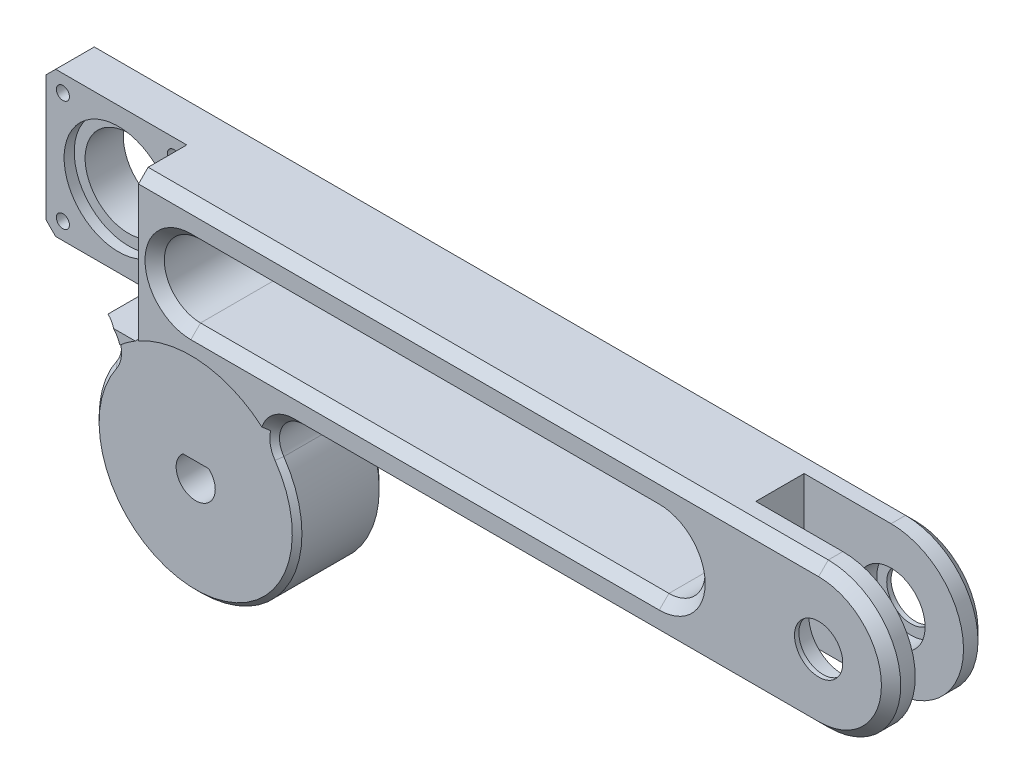
SolidWorks part; units mm, degrees
ref_plane "前视基准面" through (0, 0, 0) normal (0, 0, 1) x (1, 0, 0)
ref_plane "上视基准面" through (0, 0, 0) normal (0, 1, 0) x (1, 0, 0)
ref_plane "右视基准面" through (0, 0, 0) normal (1, 0, 0) x (0, 0, -1)
sketch "草图1" plane through (0, 0, 0) normal (0, 0, 1) x (1, 0, 0)
  line L0 (0, 15) -> (170, 15)
  line L1 (0, -15) -> (18.6465, -15)
  line L2 (0, -15) -> (0, 15)
  line L3 (61.3535, -15) -> (170, -15)
  line L4 (170, 0) -> (40, -34.8334) construction
  arc A1 (170, -15) -> (170, 15) centre (170, 0) ccw
  arc A2 (22.753, -22.8526) -> (57.247, -22.8526) centre (40, -34.8334) ccw
  arc A3 (18.6465, -15) -> (22.753, -22.8526) centre (18.6465, -20) cw
  arc A4 (61.3535, -15) -> (57.247, -22.8526) centre (61.3535, -20) ccw
  dimension "D1" = 15
  dimension "D3" = 42
  dimension "D6" = 5
  dimension "D7" = 5
  dimension "D2" = 170
  dimension "D4" = 75
  dimension "D5" = 40
extrude "凸台-拉伸1" add sketch "草图1" along normal blind 20
chamfer "倒角1" distance 2 angle 45 2 edges at (0, -15, 10) (0, 15, 10)
sketch "草图5" plane through (0, 0, 0) normal (0, 0, -1) x (-1, 0, 0)
  circle A0 centre (-170, 0) radius 5
  dimension "D1" = 10
extrude "切除-拉伸4" cut sketch "草图5" against normal blind 5
sketch "草图3" plane through (0, 15, 0) normal (0, 1, 0) x (1, 0, 0)
  line L0 (170, -20) -> (170, 0) construction
  line L1 (188, -5) -> (152, -5)
  line L2 (188, -5) -> (188, -15)
  line L3 (188, -15) -> (152, -15)
  line L4 (152, -5) -> (152, -15)
  line L5 (188, -5) -> (152, -15) construction
  line L6 (188, -15) -> (152, -5) construction
  point P0 (170, -10)
  dimension "D1" = 10
  dimension "D2" = 18
extrude "切除-拉伸2" cut sketch "草图3" against normal through all
sketch "草图4" plane through (0, 0, 0) normal (0, 0, -1) x (-1, 0, 0)
  line L0 (-40, 0) -> (-137, 0) construction
  line L1 (-40, -7.5) -> (-137, -7.5)
  line L2 (-40, 7.5) -> (-137, 7.5)
  line L3 (0, 13) -> (0, -13) construction
  arc A0 (-40, -7.5) -> (-40, 7.5) centre (-40, 0) ccw
  arc A1 (-137, 7.5) -> (-137, -7.5) centre (-137, 0) ccw
  point P3 (-88.5, 0)
  dimension "D1" = 15
  dimension "D2" = 40
  dimension "D3" = 15
extrude "切除-拉伸3" cut sketch "草图4" against normal through all
chamfer "倒角2" distance 2 angle 45 8 edges at (144.5, 0, 20) (88.5, 7.5, 20) (88.5, -7.5, 20) (32.5, 0, 20) (144.5, 0, 0) (88.5, 7.5, 0) (88.5, -7.5, 0) (32.5, 0, 0)
chamfer "倒角3" distance 2 angle 45 7 edges at (10.3233, -15, 0) (23.0773, -17.683, 0) (40, -55.8334, 0) (56.9227, -17.683, 0) (115.6767, -15, 0) (185, 0, 0) (86, 15, 0)
chamfer "倒角4" distance 2 angle 45 7 edges at (10.3233, -15, 20) (23.0773, -17.683, 20) (40, -55.8334, 20) (56.9227, -17.683, 20) (115.6767, -15, 20) (185, 0, 20) (86, 15, 20)
ref_plane "基准面1" through (0, 0, 10) normal (0, 0, -1) x (-1, 0, 0)
mirror "镜向1" about plane through (0, 0, 10) normal (0, 0, -1) of "切除-拉伸4"
sketch "草图6" plane through (0, 0, 10) normal (0, 0, -1) x (-1, 0, 0)
  point P0 (-40, -34.8334)
sketch "草图7" plane through (0, 0, 10) normal (0, 0, -1) x (-1, 0, 0)
  line L0 (-170, 0) -> (-40, -34.8334) construction
sketch "草图8" plane through (0, 0, 0) normal (0, 0, -1) x (-1, 0, 0)
  line L0 (-170, 0) -> (-15, 0) construction
  line L2 (-0.85, -15.5) -> (-29.15, -15.5)
  line L3 (-0.85, -15.5) -> (-0.85, 15.5)
  line L4 (-0.85, 15.5) -> (-29.15, 15.5)
  line L5 (-29.15, -15.5) -> (-29.15, 15.5)
  line L6 (-0.85, -15.5) -> (-29.15, 15.5) construction
  line L7 (-0.85, 15.5) -> (-29.15, -15.5) construction
  point P0 (-15, 0)
  dimension "D1" = 155
  dimension "D2" = 28.3
  dimension "D3" = 31
extrude "切除-拉伸5" cut sketch "草图8" along normal blind 10 from surface starting at face at (165, 0, 20)
sketch "草图9" plane through (0, 0, 10) normal (0, 0, 1) x (1, 0, 0)
  line L1 (3.5, -11.5) -> (26.5, -11.5)
  line L2 (3.5, -11.5) -> (3.5, 11.5)
  line L3 (3.5, 11.5) -> (26.5, 11.5)
  line L4 (26.5, -11.5) -> (26.5, 11.5)
  line L5 (3.5, -11.5) -> (26.5, 11.5) construction
  line L6 (3.5, 11.5) -> (26.5, -11.5) construction
  circle A0 centre (15, 0) radius 11.25
  circle A1 centre (26.5, 11.5) radius 1.35
  circle A2 centre (3.5, 11.5) radius 1.35
  circle A3 centre (3.5, -11.5) radius 1.35
  circle A4 centre (26.5, -11.5) radius 1.35
  line M5 (2, 15) -> (0.85, 13.85)
  line M7 (0.85, -13.85) -> (2, -15)
  dimension "D1" = 22.5
  dimension "D3" = 2.7
  dimension "D2" = 23
  dimension "D4" = 23
extrude "切除-拉伸6" cut sketch "草图9" against normal blind 2.1 contours A0 region at (15, 0, 10)
extrude "切除-拉伸7" cut sketch "草图9<3>" against normal through all contours L3 A2 L2 M5 | L4 A1 L3 | L3 A1 L4 | L1 A4 L4 | L2 A2 L3 | L4 A4 L1 | L2 A3 L1 M7 | L1 A3 L2 | A2 region at (4.073, -10.927, 10) region at (3.309, -11.691, 10) region at (25.927, -10.927, 10) region at (26.691, -11.691, 10) region at (3.309, 11.691, 10) region at (4.073, 10.927, 10) region at (25.927, 10.927, 10) region at (26.691, 11.691, 10)
sketch "草图9<3>" plane through (0, 0, 10) normal (0, 0, 1) x (1, 0, 0) same geometry as "草图9"
sketch "草图10" plane through (0, 0, 20) normal (0, 0, 1) x (1, 0, 0)
  line L0 (40, -34.8334) -> (40, -30.7834) construction
  line L1 (37.3354, -31.7834) -> (42.6646, -31.7834)
  circle A0 centre (40, -34.8334) radius 4.05
  dimension "D1" = 8.1
  dimension "D2" = 3.05
extrude "切除-拉伸8" cut sketch "草图10" against normal through all contours L1 A0 region at (40, -35.0968, 20)
sketch "草图11" plane through (0, 15, 0) normal (0, 1, 0) x (1, 0, 0)
  line L0 (3.5, -10) -> (26.5, -10) construction
  line L1 (11.827, -10) -> (-9.3552, -10)
  line L2 (11.827, -10) -> (11.827, -21.8788)
  line L3 (11.827, -21.8788) -> (-9.3552, -21.8788)
  line L4 (-9.3552, -10) -> (-9.3552, -21.8788)
extrude "切除-拉伸9" cut sketch "草图11" against normal through all
sketch "草图12" plane through (0, 0, 7.9) normal (0, 0, 1) x (1, 0, 0)
  circle A0 centre (15, 0) radius 9
  dimension "D1" = 18
extrude "切除-拉伸10" cut sketch "草图12" against normal through all
sketch "草图13" plane through (0, 0, 15) normal (0, 0, -1) x (-1, 0, 0)
  circle A0 centre (-170, 0) radius 7.05
  dimension "D1" = 14.1
extrude "切除-拉伸11" cut sketch "草图13" against normal blind 4.1
mirror "镜向2" about plane through (0, 0, 10) normal (0, 0, -1) of "切除-拉伸11"
sketch "草图14" plane through (0, 0, 20) normal (0, 0, 1) x (1, 0, 0)
  circle A0 centre (40, -34.8334) radius 22.5
  dimension "D1" = 45
extrude "切除-拉伸12" cut sketch "草图14" against normal blind 1
mirror "镜向3" about plane through (0, 0, 10) normal (0, 0, -1) of "切除-拉伸12"
